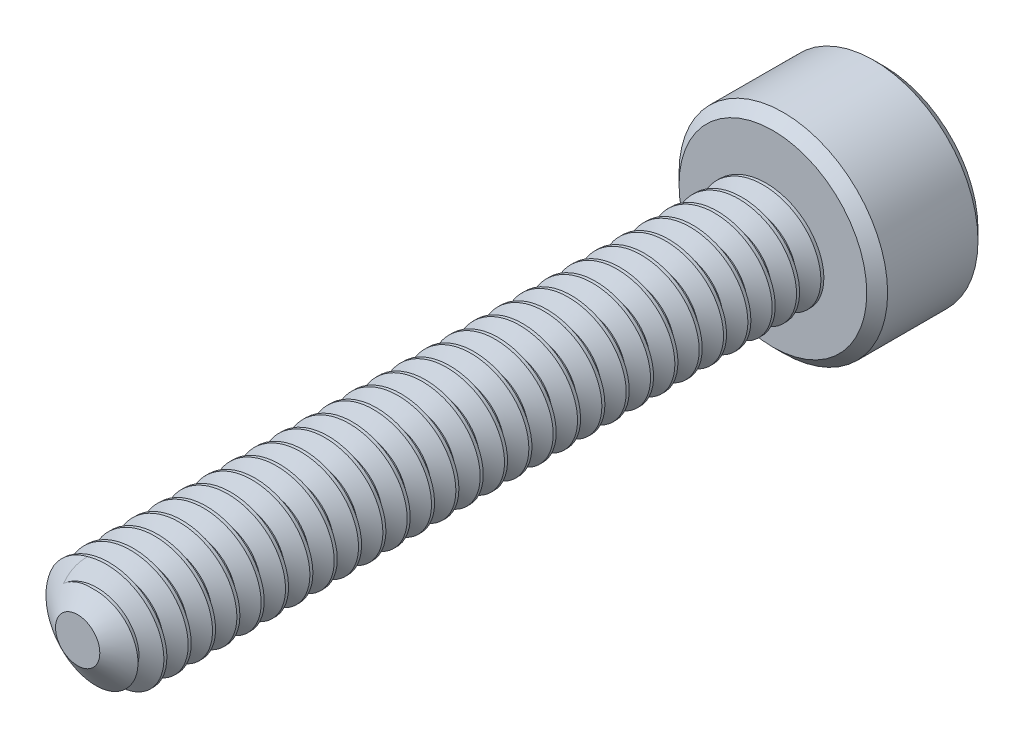
SolidWorks part; units mm, degrees
other "DetailItem1"
ref_plane "Front Plane" through (0, 0, 0) normal (0, 0, 1) x (1, 0, 0)
ref_plane "Top Plane" through (0, 0, 0) normal (0, 1, 0) x (1, 0, 0)
ref_plane "Right Plane" through (0, 0, 0) normal (1, 0, 0) x (0, 0, -1)
sketch "Sketch1" plane through (0, 0, 0) normal (0, 0, 1) x (1, 0, 0)
  circle A0 centre (0, 0) radius 0.8
  dimension "OD" = 1.6
extrude "Extrude1" add sketch "Sketch1" against normal blind 10
sketch "Sketch2" plane through (0, 0, 0) normal (0, 0, 1) x (1, 0, 0)
  circle A0 centre (0, 0) radius 0.8 construction
  circle A1 centre (0, 0) radius 0.8
curve "Helix/Spiral1" pitch 0.35 height 10.35 turns 29.5714 parameters "pitch"=0.35
sketch "Sketch3" plane through (0, 0, 0) normal (1, 0, 0) x (0, 0, -1)
  line L0 (-0.3063, 0.8) -> (-0.175, 0.5727)
  line L1 (-0.175, 0.5727) -> (-0.1313, 0.5727)
  line L2 (-0.1313, 0.5727) -> (0, 0.8)
  line L3 (-0.3063, 0.8) -> (0, 0.8)
  line L4 (-0.1531, 0.8) -> (-0.1531, 0.5727) construction
  line L5 (-0.2406, 0.6863) -> (-0.0656, 0.6863) construction
  line L6 (0, 0.8) -> (0, -0.8) construction
  dimension "D1" = 0.0437
  dimension "D2" = 0.175
  dimension "D3" = 60
sweep "Cut-Sweep1" cut profiles "Sketch3" path "Helix/Spiral1"
sketch "Sketch4" plane through (0, 0, 0) normal (1, 0, 0) x (0, 0, -1)
  line L0 (0.337, 0.8) -> (0, 0.3187)
  line L1 (0, 0.3187) -> (0, 0.8)
  line L2 (0.337, 0.8) -> (0, 0.8)
  line L3 (-0.3063, 0.8) -> (0, 0.8) construction
  line L4 (0, 0) -> (7.0209, 0) construction
  dimension "D1" = 55
  dimension "D2" = 0.254
revolve "Cut-Revolve1" cut sketch "Sketch4" angle 360 about L4
sketch "Sketch6" plane through (0, 0, -10) normal (0, 0, -1) x (-1, 0, 0)
  circle A0 centre (0, 0) radius 1.5
  dimension "head dia" = 3
extrude "Extrude2" add sketch "Sketch6" along normal blind 1.6
sketch "Sketch7" plane through (0, 0, -11.6) normal (0, 0, -1) x (-1, 0, 0)
  line L1 (0, 0.866) -> (-0.75, 0.433)
  line L2 (-0.75, 0.433) -> (-0.75, -0.433)
  line L3 (-0.75, -0.433) -> (0, -0.866)
  line L4 (0, -0.866) -> (0.75, -0.433)
  line L5 (0.75, -0.433) -> (0.75, 0.433)
  line L6 (0.75, 0.433) -> (0, 0.866)
  circle A0 centre (0, 0) radius 0.75 construction
  dimension "hex dia" = 1.5
extrude "Cut-Extrude1" cut sketch "Sketch7" against normal blind 1.125
sketch "Sketch8" plane through (0, 0, -11.6) normal (0, 0, -1) x (-1, 0, 0)
  circle A0 centre (0, 0) radius 0.866
extrude "Cut-Extrude2" cut sketch "Sketch8" against normal through all draft 45
chamfer "Chamfer1" distance 0.15 angle 45 2 edges at (-1.5, 0, -11.6) (-1.5, 0, -10)
sketch "Sketch10" plane through (0, 0, -10) normal (0, 0, 1) x (1, 0, 0)
  circle A1 centre (0, 0) radius 0.8
  circle A2 centre (0, 0) radius 0.8
  dimension "D1" = 0
ref_plane "Plane1" through (0, 0, 0) normal (0, 0, 1) x (1, 0, 0)
extrude "partial thread" [suppressed] add sketch "Sketch10" along normal up to surface (2 mm away) separate body
chamfer "Chamfer2" [suppressed] distance 0.032 angle 45
combine bodies "Combine1" [suppressed] operation type add bodies to combine 107 108
sketch "Sketch9" plane through (0, 0, 0) normal (1, 0, 0) x (0, 0, -1)
  line L0 (0, 0.8) -> (0, -0.8) construction
  line L1 (0.875, 0.8) -> (0.875, -0.8) construction
  dimension "D1" = 0.875
  dimension "D4" = 0.635
  dimension "D5" = 0.3302
equation "\"D3@Helix/Spiral1\" = \"screw length@Extrude1\"+\"pitch@Helix/Spiral1\""
equation "\"D1@Sketch3\" = \"pitch@Helix/Spiral1\"*.125"
equation "\"D2@Sketch3\" = \"pitch@Helix/Spiral1\"*.5"
equation "\"D1@Cut-Extrude1\" = \"hex dia@Sketch7\"*.75"
equation "\"D1@Chamfer1\" = \"head dia@Sketch6\"*.05"
equation "\"D1@Sketch9\" = \"pitch@Helix/Spiral1\"*2.5"
equation "\"D1@Chamfer2\"=\"OD@Sketch1\"*.02"
